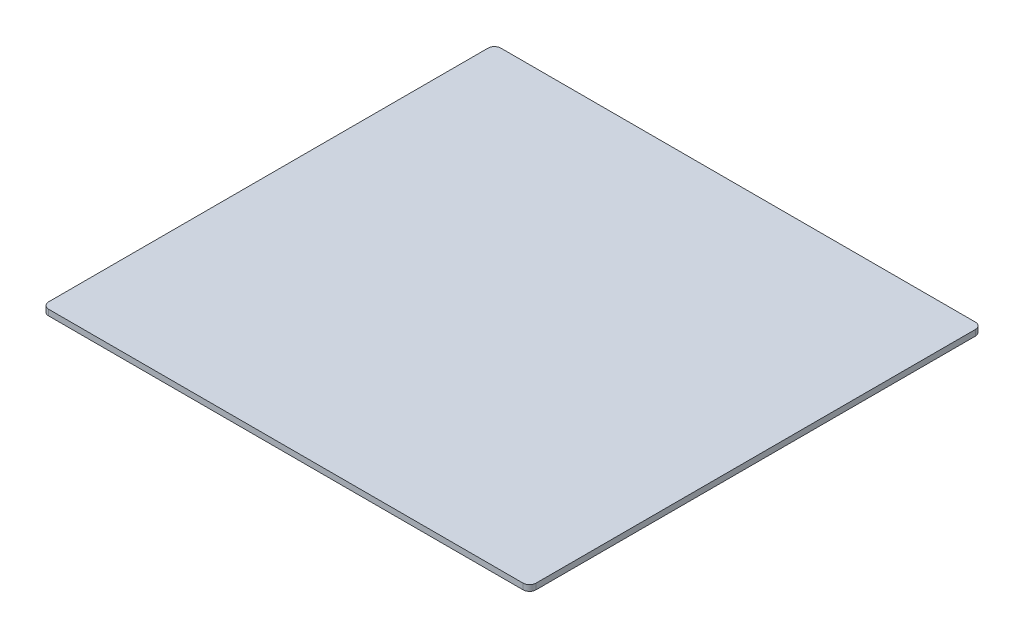
SolidWorks part; units mm, degrees
ref_plane "Front Plane" through (0, 0, 0) normal (0, 0, 1) x (1, 0, 0)
ref_plane "Top Plane" through (0, 0, 0) normal (0, 1, 0) x (1, 0, 0)
ref_plane "Right Plane" through (0, 0, 0) normal (1, 0, 0) x (0, 0, -1)
sketch "Sketch1" plane through (0, 0, 0) normal (0, 1, 0) x (1, 0, 0)
  line L1 (-380, 352.65) -> (380, 352.65)
  line L2 (-380, 352.65) -> (-380, -352.65)
  line L3 (-380, -352.65) -> (380, -352.65)
  line L4 (380, 352.65) -> (380, -352.65)
  point P4 (0, -352.65)
  point P5 (-380, 0)
  dimension "D1" = 705.3
  dimension "D2" = 760
extrude "Boss-Extrude1" add sketch "Sketch1" along normal blind 23.2 contours L2 L3 L4 L1
sketch "Sketch2" plane through (0, 0, 0) normal (0, -1, 0) x (1, 0, 0)
  line L0 (-380, -352.65) -> (380, -352.65) construction
  line L1 (-225, 306.65) -> (225, 306.65)
  line L2 (-225, 306.65) -> (-225, -306.65)
  line L3 (-225, -306.65) -> (225, -306.65)
  line L4 (225, 306.65) -> (225, -306.65)
  line L5 (-380, -352.65) -> (-380, 352.65) construction
  line L6 (380, -352.65) -> (380, 352.65) construction
  line L7 (-380, 352.65) -> (380, 352.65) construction
  line L8 (-380, -352.65) -> (380, -352.65)
  line L9 (380, -352.65) -> (380, 352.65)
  line L10 (-380, 352.65) -> (380, 352.65)
  line L11 (-380, -352.65) -> (-380, 352.65)
  dimension "D1" = 46
  dimension "D2" = 155
  dimension "D3" = 155
  dimension "D4" = 46
extrude "Cut-Extrude1" cut sketch "Sketch2" against normal blind 14.1
chamfer "Chamfer3" distance 9.1 distance2 14.1 4 edges at (0, 14.1, 306.65) (225, 14.1, 0) (0, 14.1, -306.65) (-225, 14.1, 0) first distance on face at (0, 14.1, 0)
fillet "Fillet2" radius 13 4 edges at (-229.55, 7.05, -311.2) (-229.55, 7.05, 311.2) (229.55, 7.05, 311.2) (229.55, 7.05, -311.2)
fillet "Fillet3" radius 10 4 edges at (380, 18.65, -352.65) (380, 18.65, 352.65) (-380, 18.65, 352.65) (-380, 18.65, -352.65)
shell "Shell1" thickness 1 removed face at (0, 23.2, 0)
sketch "Sketch3" plane through (0, 23.2, 0) normal (0, 1, 0) x (1, 0, 0)
  line L0 (-370, 352.65) -> (370, 352.65) construction
  line L1 (380, 342.65) -> (380, -342.65) construction
  line L2 (-370, -352.65) -> (370, -352.65) construction
  line L3 (-380, 342.65) -> (-380, -342.65) construction
  line L4 (-370, 352.65) -> (370, 352.65)
  line L5 (380, 342.65) -> (380, -342.65)
  line L6 (-370, -352.65) -> (370, -352.65)
  line L7 (-380, 342.65) -> (-380, -342.65)
  arc A0 (-370, 352.65) -> (-380, 342.65) centre (-370, 342.65) ccw construction
  arc A1 (380, 342.65) -> (370, 352.65) centre (370, 342.65) ccw construction
  arc A2 (370, -352.65) -> (380, -342.65) centre (370, -342.65) ccw construction
  arc A3 (-380, -342.65) -> (-370, -352.65) centre (-370, -342.65) ccw construction
  arc A4 (-370, 352.65) -> (-380, 342.65) centre (-370, 342.65) ccw
  arc A5 (380, 342.65) -> (370, 352.65) centre (370, 342.65) ccw
  arc A6 (370, -352.65) -> (380, -342.65) centre (370, -342.65) ccw
  arc A7 (-380, -342.65) -> (-370, -352.65) centre (-370, -342.65) ccw
extrude "Boss-Extrude2" add sketch "Sketch3" against normal blind 1
